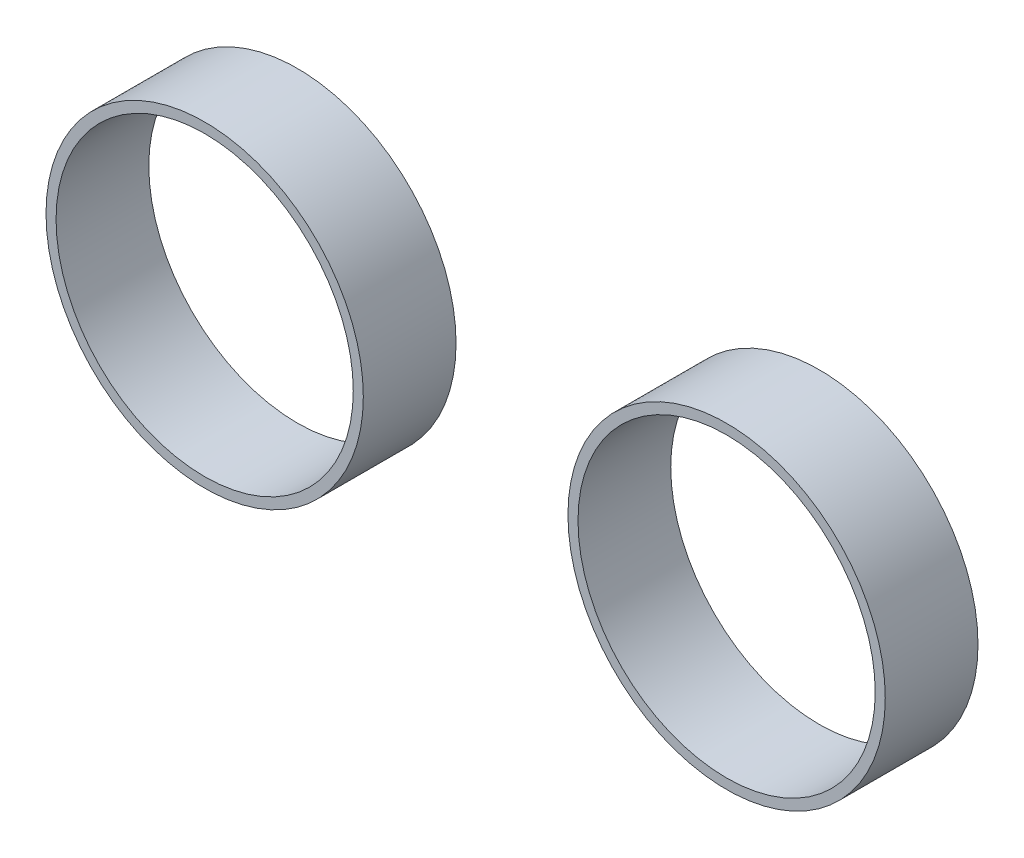
SolidWorks part; units mm, degrees
material "Velcro"
ref_plane "Front Plane" through (0, 0, 0) normal (0, 0, 1) x (1, 0, 0)
ref_plane "Top Plane" through (0, 0, 0) normal (0, 1, 0) x (1, 0, 0)
ref_plane "Right Plane" through (0, 0, 0) normal (1, 0, 0) x (0, 0, -1)
sketch "Sketch1" plane through (0, 0, 0) normal (0, 0, 1) x (1, 0, 0)
  circle A0 centre (1664.2805, -423.3823) radius 69.4 construction
  circle A1 centre (1664.2805, -423.3823) radius 65 construction
  circle A2 centre (1435.9805, -423.3823) radius 69.4 construction
  circle A3 centre (1435.9805, -423.3823) radius 65 construction
  circle A4 centre (1664.2805, -423.3823) radius 69.4
  circle A5 centre (1664.2805, -423.3823) radius 65
  circle A6 centre (1435.9805, -423.3823) radius 69.4
  circle A7 centre (1435.9805, -423.3823) radius 65
extrude "Boss-Extrude1" add sketch "Sketch1" against normal blind 40.56
